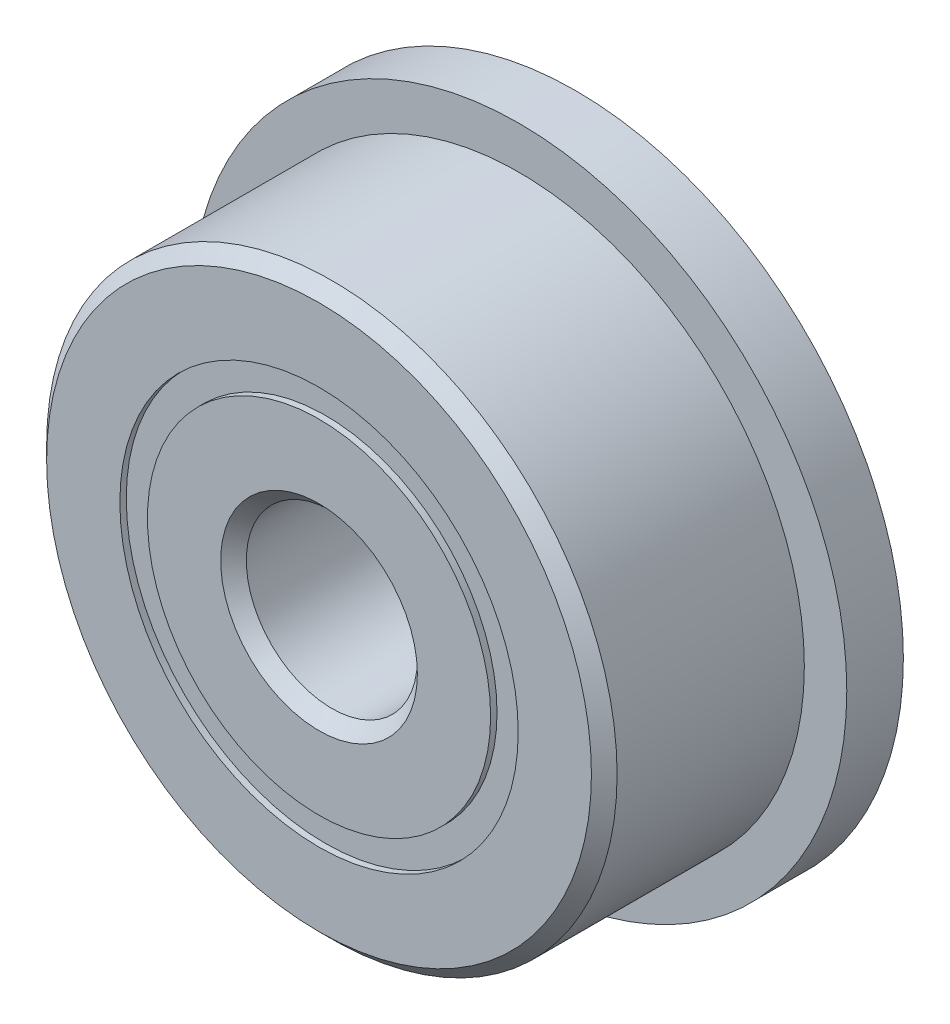
SolidWorks part; units mm, degrees
material "AISI 316 Annealed Stainless Steel Bar (SS)"
ref_plane "Front Plane" through (0, 0, 0) normal (0, 0, 1) x (1, 0, 0)
ref_plane "Top Plane" through (0, 0, 0) normal (0, 1, 0) x (1, 0, 0)
ref_plane "Right Plane" through (0, 0, 0) normal (1, 0, 0) x (0, 0, -1)
sketch "Sketch1" plane through (0, 0, 0) normal (1, 0, 0) x (0, 0, -1)
  line L0 (-1.7856, 0) -> (1.7856, 0) construction
  line L1 (0, 3.9688) -> (0, -3.9688) construction
  line L2 (1.6071, 3.9688) -> (-1.6071, 3.9688)
  line L3 (-1.6071, 3.9688) -> (-1.7856, 3.7902)
  line L4 (-1.7856, 3.7902) -> (-1.7856, 2.7713)
  line L5 (-1.7856, 2.7713) -> (-0.7936, 2.7713)
  line L6 (1.7856, 2.7713) -> (0.7936, 2.7713)
  line L7 (1.7856, 3.7902) -> (1.7856, 2.7713)
  line L8 (1.6071, 3.9688) -> (1.7856, 3.7902)
  line L9 (0, 3.9688) -> (0, 2.5794) construction
  line L10 (0, 2.5794) -> (0, 1.19) construction
  arc A0 (-0.7936, 2.7713) -> (0.7936, 2.7713) centre (0, 2.5794) cw
  point P14 (0, 1.19)
  dimension "Width" = 3.5712
  dimension "OD" = 7.9375
  dimension "D1" = 45
  dimension "D2" = 0.1786
  dimension "Shaft Dia" = 2.38
  dimension "D3" = 1.5872
  dimension "D4" = 0.1919
revolve "Revolve1" add sketch "Sketch1" angle 360 about L0
sketch "Sketch3" plane through (0, 0, 0) normal (1, 0, 0) x (0, 0, -1)
  line L0 (-1.7856, 2.3874) -> (-0.7936, 2.3874)
  line L1 (0, 3.9688) -> (0, -3.9688) construction
  line L2 (-1.7856, 3.7902) -> (-1.7856, 2.7713) construction
  line L3 (-1.7856, 2.3874) -> (-1.7856, 1.3686)
  line L4 (-1.6071, 3.9688) -> (-1.7856, 3.7902) construction
  line L5 (-1.7856, 1.3686) -> (-1.6071, 1.19)
  line L6 (-1.6071, 1.19) -> (1.6071, 1.19)
  line L7 (1.6071, 3.9688) -> (1.6071, -3.9688) construction
  line L8 (1.6071, 1.19) -> (1.7856, 1.3686)
  line L9 (1.7856, -3.7902) -> (1.7856, 3.7902) construction
  line L10 (1.7856, 1.3686) -> (1.7856, 2.3874)
  line L11 (1.7856, 2.3874) -> (0.7936, 2.3874)
  line L13 (1.6071, 3.9688) -> (1.7856, 3.7902) construction
  arc A0 (0.7936, 2.7713) -> (-0.7936, 2.7713) centre (0, 2.5794) ccw construction
  arc A1 (0.7936, 2.3874) -> (-0.7936, 2.3874) centre (0, 2.5794) cw
revolve "Revolve3" add sketch "Sketch3" angle 360 about L0
sketch "Sketch4" plane through (0, 0, 0) normal (1, 0, 0) x (0, 0, -1)
  line L0 (-0.8165, 2.5794) -> (0.8165, 2.5794)
  arc A2 (-0.8165, 2.5794) -> (0.8165, 2.5794) centre (0, 2.5794) cw
  arc A3 (0.7936, 2.7713) -> (-0.7936, 2.7713) centre (0, 2.5794) ccw construction
revolve "Revolve4" add sketch "Sketch4" angle 360 about L0
ref_axis "Axis1" through (0, 0, -1.7856) along (0, 0, 1)
pattern_circular "CirPattern1" count 12 every 30 about axis through (0, 0, -1.7856) along (0, 0, 1) of bodies 104
sketch "Sketch5" plane through (0, 0, 0) normal (1, 0, 0) x (0, 0, -1)
  line L0 (-1.7856, 2.7713) -> (-0.7936, 2.7713) construction
  line L1 (-1.6963, 2.7713) -> (-0.8165, 2.7713)
  line L2 (-1.6963, 2.7713) -> (-1.6963, 2.3874)
  line L3 (-1.6963, 2.3874) -> (-0.8165, 2.3874)
  line L4 (-0.8165, 2.7713) -> (-0.8165, 2.3874)
  line L5 (-1.7856, 2.3874) -> (-0.7936, 2.3874) construction
  line L6 (1.7856, 2.7713) -> (0.7936, 2.7713) construction
  line L7 (1.6963, 2.7713) -> (0.8165, 2.7713)
  line L8 (1.6963, 2.7713) -> (1.6963, 2.3874)
  line L9 (1.6963, 2.3874) -> (0.8165, 2.3874)
  line L10 (0.8165, 2.7713) -> (0.8165, 2.3874)
  line L11 (1.7856, 2.3874) -> (0.7936, 2.3874) construction
  line L12 (-1.6071, 3.9688) -> (-1.7856, 3.7902) construction
  point P18 (-1.6963, 3.8795)
revolve "Revolve5" add sketch "Sketch5" angle 360 about L0
sketch "Sketch6" plane through (0, 0, 0) normal (1, 0, 0) x (0, 0, -1)
  line L0 (1.7856, 0) -> (-1.7856, 0) construction
  line L1 (1.7856, 2.7713) -> (0.9982, 2.7713)
  line L2 (1.7856, 2.7713) -> (1.7856, 4.5593)
  line L3 (1.7856, 4.5593) -> (0.9982, 4.5593)
  line L4 (0.9982, 2.7713) -> (0.9982, 4.5593)
  dimension "Th" = 0.7874
  dimension "Flange OD" = 9.1186
revolve "Revolve6" add sketch "Sketch6" angle 360 about L0
equation "\"D2@Sketch1\" = \"Width@Sketch1\"*.05"
equation "\"D3@Sketch1\" = \"Width@Sketch1\"/2.25"
equation "\"D4@Sketch1\" = (((\"OD@Sketch1\"-\"Width@Sketch1\")/2)/3.25)/3.5"
equation "\"D2@CirPattern1\" = 360/\"Balls@CirPattern1\""
